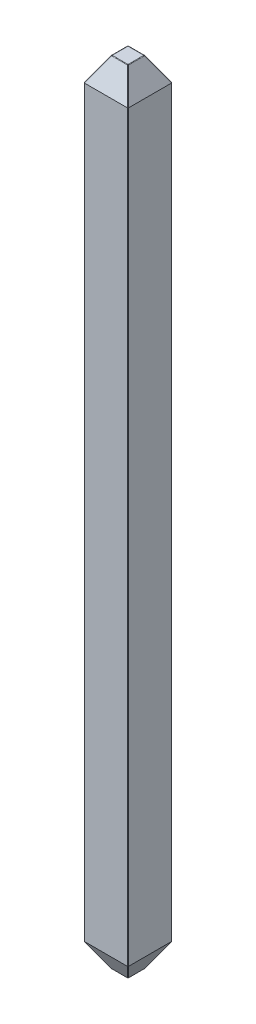
SolidWorks part; units mm, degrees
ref_plane "前视基准面" through (0, 0, 0) normal (0, 0, 1) x (1, 0, 0)
ref_plane "上视基准面" through (0, 0, 0) normal (0, 1, 0) x (1, 0, 0)
ref_plane "右视基准面" through (0, 0, 0) normal (1, 0, 0) x (0, 0, -1)
sketch "Sketch1" plane through (0, 0, 0) normal (0, 1, 0) x (1, 0, 0)
  line L1 (-0.32, 0.32) -> (0.32, 0.32)
  line L2 (-0.32, 0.32) -> (-0.32, -0.32)
  line L3 (-0.32, -0.32) -> (0.32, -0.32)
  line L4 (0.32, 0.32) -> (0.32, -0.32)
  line L5 (-0.32, 0.32) -> (0.32, -0.32) construction
  line L6 (-0.32, -0.32) -> (0.32, 0.32) construction
  point P0 (0, 0)
  dimension "D1" = 0.64
  dimension "D2" = 0.64
extrude "Boss-Extrude1" add sketch "Sketch1" along normal blind 11.5
chamfer "Chamfer1" distance 0.2 angle 60 4 edges at (0, 11.5, 0.32) (-0.32, 11.5, 0) (0, 11.5, -0.32) (0.32, 11.5, 0) first distance on face at (0, 11.5, 0)
chamfer "Chamfer2" distance 0.2 angle 60 4 edges at (0, 0, -0.32) (-0.32, 0, 0) (0, 0, 0.32) (0.32, 0, 0) first distance on face at (0, 0, 0)
fillet "Fillet2" radius 0.01 20 edges at (-0.12, 11.5, 0) (0, 11.5, 0.12) (0.12, 11.5, 0) (0, 11.5, -0.12) (0.22, 11.3268, -0.22) (-0.22, 11.3268, -0.22) (-0.22, 11.3268, 0.22) (0.22, 11.3268, 0.22) (-0.12, 0, 0) (0, 0, -0.12) (0, 0, 0.12) (0.12, 0, 0) (-0.22, 0.1732, -0.22) (-0.22, 0.1732, 0.22) (0.22, 0.1732, -0.22) (0.22, 0.1732, 0.22) (-0.32, 5.75, -0.32) (0.32, 5.75, -0.32) (0.32, 5.75, 0.32) (-0.32, 5.75, 0.32)
